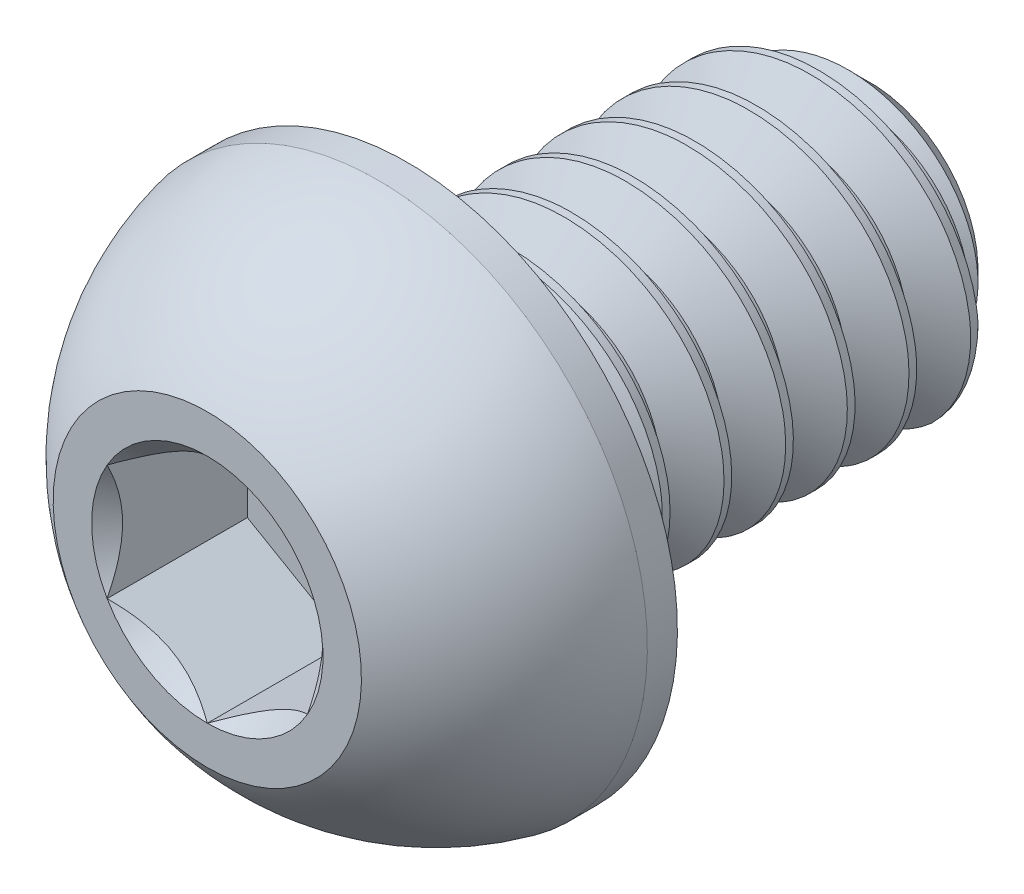
SolidWorks part; units mm, degrees
material "Stainless Steel (ferritic)"
ref_plane "Front" through (0, 0, 0) normal (0, 0, 1) x (1, 0, 0)
ref_plane "Top" through (0, 0, 0) normal (0, 1, 0) x (1, 0, 0)
ref_plane "Right" through (0, 0, 0) normal (1, 0, 0) x (0, 0, -1)
sketch "Sketch1" plane through (0, 0, 0) normal (1, 0, 0) x (0, 0, -1)
  line L2 (-1.5, 1) -> (1.5, 1)
  line L3 (1.5, 1) -> (1.5, 0)
  line L4 (1.5, 0) -> (-1.5, 0)
  line L6 (-1.695, 1.75) -> (-1.5, 1.75) construction
  line L7 (1.5, 1) -> (1.5, -1) construction
  line L8 (-2.8, 0) -> (-1.5, 0) construction
  line L9 (-1.5, 1.75) -> (-1.5, -1.75) construction
  line L11 (-1.5, 1) -> (-1.5, 0)
  line L13 (-2.8, 0.65) -> (-2.8, -0.65) construction
  line L14 (-2.8, 0.65) -> (-2.8, 1) construction
  line L15 (1.475, 1.0433) -> (1.675, 0.6969) construction
  line L16 (1.675, 0.6969) -> (1.875, 1.0433) construction
  line L17 (1.875, 1.0433) -> (1.475, 1.0433) construction
  line L18 (1.5, 1) -> (1.85, 1) construction
  line L19 (1.675, 1.0433) -> (1.675, 1) construction
  line L20 (1.675, 1) -> (1.675, 0.7402) construction
  line L21 (1.675, 0.7402) -> (1.675, 0.6969) construction
  line L22 (1.65, 0.7402) -> (1.7, 0.7402)
  line L23 (1.4875, 1.0217) -> (1.8625, 1.0217)
  line L24 (1.7, 0.7402) -> (1.8625, 1.0217)
  line L25 (1.65, 0.7402) -> (1.4875, 1.0217)
  line L26 (1.2, 1) -> (1.5, 0.7)
  arc A3 (-2.8, 1) -> (-1.695, 1.75) centre (-1.3142, 0) cw construction
  point P29 (1.675, 1.0217)
  point P30 (0.5, -1)
  point P33 (0, 0)
  dimension "Thread Size" = 2
  dimension "D1" = 0.195
  dimension "Head Height" = 1.3
  dimension "Head Diameter" = 3.5
  dimension "Length" = 3
  dimension "Drive Size" = 1.3
  dimension "Thread Pitch" = 0.4
  dimension "D3" = 0.05
  dimension "D2" = 0.3
  dimension "D4" = 45
  dimension "D5" = 1
sketch "Sketch10" plane through (0, 0, 0) normal (1, 0, 0) x (0, 0, -1)
  line L0 (1.2, 1) -> (1.5, 0.7) construction
  line L1 (1.2, 1) -> (1.5, 0.7)
  line L4 (1.5, 1) -> (-1.5, 1)
  line L5 (1.5, 0) -> (1.5, 1)
  line L6 (-1.5, 0) -> (1.5, 0)
  line L7 (-1.5, 1) -> (-1.5, 0)
  line L8 (1.2, 1) -> (-1.5, 1)
  line L9 (1.5, 0) -> (1.5, 0.7)
  line L10 (-1.5, 0) -> (1.5, 0)
  line L11 (-1.5, 1) -> (-1.5, 0)
  dimension "D1" = 0
revolve "Revolve3" add sketch "Sketch10" angle 360 about L8
sketch "Sketch7" plane through (0, 0, 0) normal (1, 0, 0) x (0, 0, -1)
  line L6 (-1.695, 1.75) -> (-1.5, 1.75) construction
  line L8 (-2.8, 0) -> (-1.5, 0) construction
  line L11 (-1.5, 1.75) -> (-1.5, -1.75) construction
  line L12 (-1.695, 1.75) -> (-1.5, 1.75)
  line L13 (-2.8, 0) -> (-1.5, 0)
  line L14 (-2.8, 0.65) -> (-2.8, -0.65) construction
  line L15 (-1.5, 1.75) -> (-1.5, 0)
  line L16 (-2.8, 1) -> (-2.8, 0)
  arc A2 (-1.695, 1.75) -> (-2.8, 1) centre (-1.3142, 0) ccw construction
  arc A3 (-1.695, 1.75) -> (-2.8, 1) centre (-1.3142, 0) ccw
revolve "Revolve2" add sketch "Sketch7" angle 360 mid plane about L13
sketch "Sketch5" plane through (0, 0, 2.8) normal (0, 0, 1) x (1, 0, 0)
  line L1 (0.65, -0.3753) -> (0.65, 0.3753)
  line L2 (0.65, 0.3753) -> (0, 0.7506)
  line L3 (0, 0.7506) -> (-0.65, 0.3753)
  line L4 (-0.65, 0.3753) -> (-0.65, -0.3753)
  line L5 (-0.65, -0.3753) -> (0, -0.7506)
  line L6 (0, -0.7506) -> (0.65, -0.3753)
  circle A0 centre (0, 0) radius 0.65 construction
extrude "Cut-Extrude2" cut sketch "Sketch5" against normal blind 0.91
sketch "Sketch6" plane through (0, 0, 2.8) normal (0, 0, 1) x (1, 0, 0)
  circle A0 centre (0, 0) radius 0.7506
extrude "Cut-Extrude3" cut sketch "Sketch6" against normal blind 0.91 draft 45
sketch "Sketch9" plane through (0, 0, 1.5) normal (0, 0, -1) x (-1, 0, 0)
  circle A0 centre (0, 0) radius 1 construction
  circle A4 centre (0, 0) radius 1
split "Split1" bodies to split 113 resulting bodies 123 124 split by face at (0, -1.75, 1.5)
sketch "Sketch11" plane through (0, 0, -1.5) normal (0, 0, -1) x (-1, 0, 0)
  circle A0 centre (0, 0) radius 1 construction
  circle A1 centre (0, 0) radius 1
curve "Helix/Spiral1" pitch 0.4 height 4.3 radius 1 centre (0, 0, -1.5) axis (0, 0, 1) start towards (0, 1, 0)
sketch "Sketch12" plane through (0, 0, 0) normal (1, 0, 0) x (0, 0, -1)
  line L0 (1.65, 0.7402) -> (1.7, 0.7402) construction
  line L1 (1.7, 0.7402) -> (1.8625, 1.0217) construction
  line L2 (1.4875, 1.0217) -> (1.8625, 1.0217) construction
  line L3 (1.65, 0.7402) -> (1.4875, 1.0217) construction
  line L4 (1.65, 0.7402) -> (1.7, 0.7402)
  line L5 (1.7, 0.7402) -> (1.8625, 1.0217)
  line L6 (1.4875, 1.0217) -> (1.8625, 1.0217)
  line L7 (1.65, 0.7402) -> (1.4875, 1.0217)
sweep "Cut-Sweep2" cut profiles "Sketch12" path "Helix/Spiral1" align with end faces yes
extrude "Boss-Extrude1" add sketch "Sketch9" along normal blind 10 draft 45
equation "\"D1@Cut-Extrude2\" = \"Head Height@Sketch1\" * .7"
equation "\"D1@Sketch1\" = \"Head Height@Sketch1\" * .15"
equation "\"D1@Cut-Extrude3\" = \"D1@Cut-Extrude2\""
equation "\"D3@Sketch1\" = \"Thread Pitch@Sketch1\" / 8"
equation "\"D2@Sketch1\" = \"Thread Pitch@Sketch1\" * 0.75"
equation "\"D3@Helix/Spiral1\" = \"Length@Sketch1\" + \"Head Height@Sketch1\""
equation "\"D4@Helix/Spiral1\" = \"Thread Pitch@Sketch1\""
equation "\"D5@Sketch1\" = \"Thread Pitch@Sketch1\" * 2.5"
